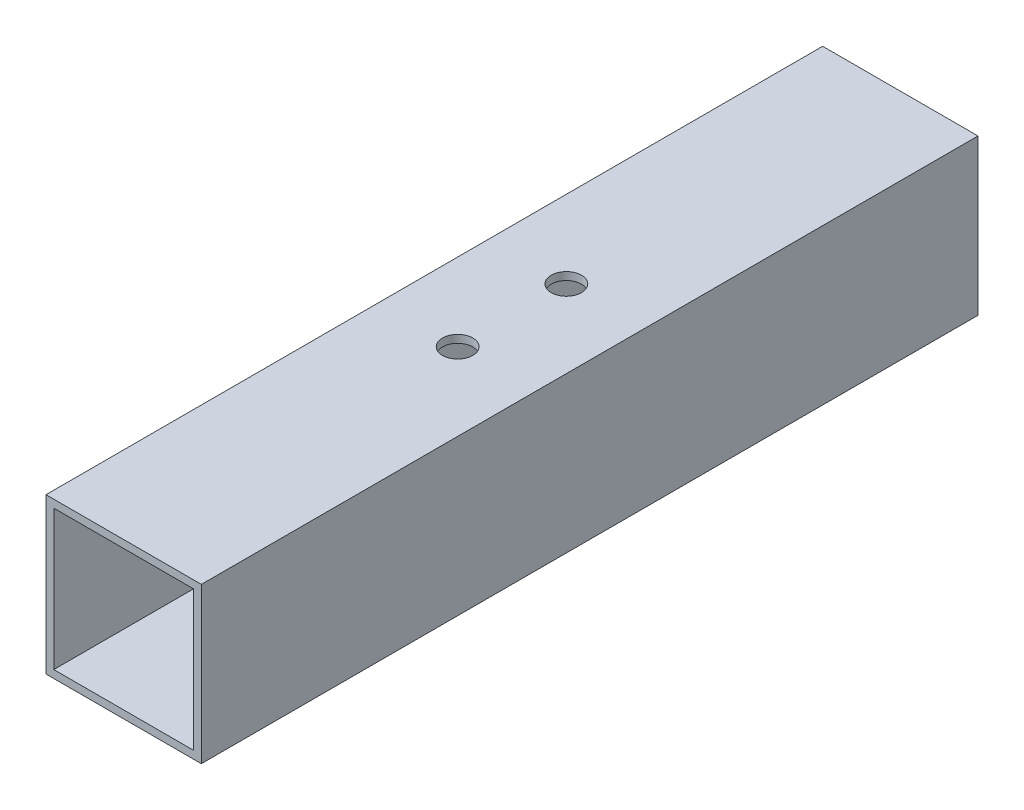
SolidWorks part; units mm, degrees
material "1060 合金"
ref_plane "前视基准面" through (0, 0, 0) normal (0, 0, 1) x (1, 0, 0)
ref_plane "上视基准面" through (0, 0, 0) normal (0, 1, 0) x (1, 0, 0)
ref_plane "右视基准面" through (0, 0, 0) normal (1, 0, 0) x (0, 0, -1)
other "Configuration Table"
sketch "草图1" plane through (0, 0, 0) normal (0, 0, 1) x (1, 0, 0)
  line L1 (0, 0) -> (20, 0)
  line L2 (0, 0) -> (0, -20)
  line L3 (0, -20) -> (20, -20)
  line L4 (20, 0) -> (20, -20)
  dimension "D1" = 20
  dimension "D2" = 20
extrude "拉伸-薄壁1" add sketch "草图1" along normal blind 100 thin thin type one direction reverse wall 1
sketch "草图2" plane through (0, -20, 0) normal (0, -1, 0) x (1, 0, 0)
  circle A1 centre (7.5, 825) radius 2.6
  circle A2 centre (7.5, 825) radius 2.6
  dimension "D1" = 0
extrude "切除-拉伸1" [suppressed] cut sketch "草图2" against normal up to next
sketch "草图3" plane through (0, -20, 0) normal (0, -1, 0) x (1, 0, 0)
  line L0 (20, 100) -> (20, 0) construction
  line L3 (0, 0) -> (20, 0) construction
  circle A0 centre (10, 57) radius 1.95
  circle A1 centre (10, 43) radius 1.95
  dimension "D1" = 3.9
  dimension "D4" = 3.9
  dimension "D2" = 10
  dimension "D3" = 14
  dimension "D5" = 43
  dimension "D6" = 10
extrude "切除-拉伸2" cut sketch "草图3" against normal through all
